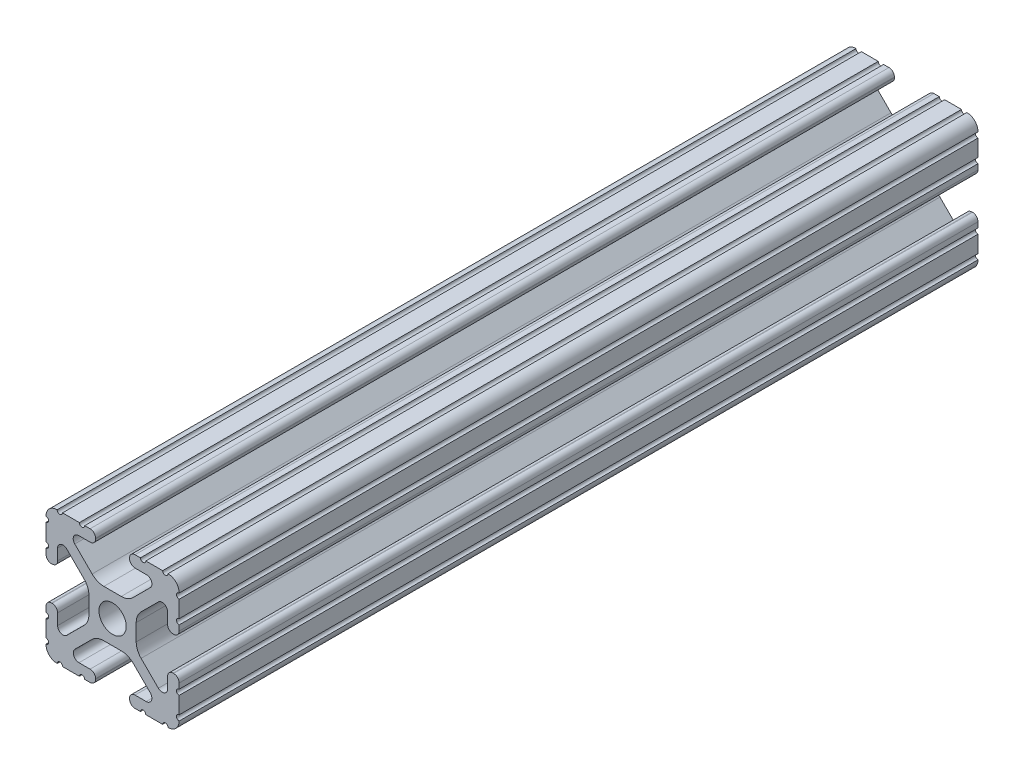
SolidWorks part; units mm, degrees
material "6061 Alloy"
ref_plane "Front Plane" through (0, 0, 0) normal (0, 0, 1) x (1, 0, 0)
ref_plane "Top Plane" through (0, 0, 0) normal (0, 1, 0) x (1, 0, 0)
ref_plane "Right Plane" through (0, 0, 0) normal (1, 0, 0) x (0, 0, -1)
sketch "Sketch1" plane through (0, 0, 0) normal (0, 0, 1) x (1, 0, 0)
  line L88 (-7.1797, -8.6452) -> (-3.9523, -5.4237)
  line L89 (-1.7093, -4.4958) -> (1.7093, -4.4958)
  line L90 (3.9523, -5.4237) -> (7.1797, -8.6452)
  line L91 (6.4164, -10.4902) -> (4.2875, -10.4902)
  line L92 (3.2385, -11.5392) -> (3.2385, -11.651)
  line L93 (4.2875, -12.7) -> (5.3171, -12.7)
  line L94 (6.3331, -12.7) -> (9.5504, -12.7)
  line L95 (12.7, -9.5504) -> (12.7, -6.3331)
  line L96 (12.7, -5.3171) -> (12.7, -4.2875)
  line L97 (11.651, -3.2385) -> (11.5392, -3.2385)
  line L98 (10.4902, -4.2875) -> (10.4902, -6.4021)
  line L99 (8.7371, -7.1294) -> (5.441, -3.8408)
  line L100 (4.5085, -1.5932) -> (4.5085, 1.5932)
  line L101 (5.441, 3.8408) -> (8.7371, 7.1294)
  line L102 (10.4902, 6.4021) -> (10.4902, 4.2875)
  line L103 (11.5392, 3.2385) -> (11.651, 3.2385)
  line L104 (12.7, 4.2875) -> (12.7, 5.3171)
  line L105 (12.7, 6.3331) -> (12.7, 9.5504)
  line L106 (9.5504, 12.7) -> (6.3331, 12.7)
  line L107 (5.3171, 12.7) -> (4.2875, 12.7)
  line L108 (3.2385, 11.651) -> (3.2385, 11.5392)
  line L109 (4.2875, 10.4902) -> (6.4768, 10.4902)
  line L110 (7.207, 8.7244) -> (3.8983, 5.4232)
  line L111 (1.6558, 4.4958) -> (-1.6558, 4.4958)
  line L112 (-3.8983, 5.4232) -> (-7.207, 8.7244)
  line L113 (-6.4768, 10.4902) -> (-4.2875, 10.4902)
  line L114 (-3.2385, 11.5392) -> (-3.2385, 11.651)
  line L115 (-4.2875, 12.7) -> (-5.3171, 12.7)
  line L116 (-6.3331, 12.7) -> (-9.5504, 12.7)
  line L117 (-12.7, 9.5504) -> (-12.7, 6.3331)
  line L118 (-12.7, 5.3171) -> (-12.7, 4.2875)
  line L119 (-11.651, 3.2385) -> (-11.5392, 3.2385)
  line L120 (-10.4902, 4.2875) -> (-10.4902, 6.4021)
  line L121 (-8.7371, 7.1294) -> (-5.441, 3.8408)
  line L122 (-4.5085, 1.5932) -> (-4.5085, -1.5932)
  line L123 (-5.441, -3.8408) -> (-8.7371, -7.1294)
  line L124 (-10.4902, -6.4021) -> (-10.4902, -4.2875)
  line L125 (-11.5392, -3.2385) -> (-11.651, -3.2385)
  line L126 (-12.7, -4.2875) -> (-12.7, -5.3171)
  line L127 (-12.7, -6.3331) -> (-12.7, -9.5504)
  line L128 (-9.5504, -12.7) -> (-6.3331, -12.7)
  line L129 (-5.3171, -12.7) -> (-4.2875, -12.7)
  line L130 (-3.2385, -11.651) -> (-3.2385, -11.5392)
  line L131 (-4.2875, -10.4902) -> (-6.4164, -10.4902)
  circle A1 centre (0, 0) radius 2.6035
  arc A104 (-7.1797, -8.6452) -> (-6.4164, -10.4902) centre (-6.4164, -9.4098) ccw
  arc A105 (-1.7093, -4.4958) -> (-3.9523, -5.4237) centre (-1.7093, -7.6708) ccw
  arc A106 (3.9523, -5.4237) -> (1.7093, -4.4958) centre (1.7093, -7.6708) ccw
  arc A107 (6.4164, -10.4902) -> (7.1797, -8.6452) centre (6.4164, -9.4098) ccw
  arc A108 (4.2875, -10.4902) -> (3.2385, -11.5392) centre (4.2875, -11.5392) ccw
  arc A109 (3.2385, -11.651) -> (4.2875, -12.7) centre (4.2875, -11.651) ccw
  arc A110 (6.3331, -12.7) -> (5.3171, -12.7) centre (5.8251, -12.7) ccw
  arc A111 (10.5664, -12.6998) -> (9.5504, -12.7) centre (10.0584, -12.7) ccw
  arc A112 (10.5664, -12.6998) -> (12.6998, -10.5664) centre (10.5918, -10.5918) ccw
  arc A113 (12.7, -9.5504) -> (12.6998, -10.5664) centre (12.7, -10.0584) ccw
  arc A114 (12.7, -5.3171) -> (12.7, -6.3331) centre (12.7, -5.8251) ccw
  arc A115 (12.7, -4.2875) -> (11.651, -3.2385) centre (11.651, -4.2875) ccw
  arc A116 (11.5392, -3.2385) -> (10.4902, -4.2875) centre (11.5392, -4.2875) ccw
  arc A117 (8.7371, -7.1294) -> (10.4902, -6.4021) centre (9.4628, -6.4021) ccw
  arc A118 (4.5085, -1.5932) -> (5.441, -3.8408) centre (7.6835, -1.5932) ccw
  arc A119 (5.441, 3.8408) -> (4.5085, 1.5932) centre (7.6835, 1.5932) ccw
  arc A120 (10.4902, 6.4021) -> (8.7371, 7.1294) centre (9.4628, 6.4021) ccw
  arc A121 (10.4902, 4.2875) -> (11.5392, 3.2385) centre (11.5392, 4.2875) ccw
  arc A122 (11.651, 3.2385) -> (12.7, 4.2875) centre (11.651, 4.2875) ccw
  arc A123 (12.7, 6.3331) -> (12.7, 5.3171) centre (12.7, 5.8251) ccw
  arc A124 (12.6998, 10.5664) -> (12.7, 9.5504) centre (12.7, 10.0584) ccw
  arc A125 (12.6998, 10.5664) -> (10.5664, 12.6998) centre (10.5918, 10.5918) ccw
  arc A126 (9.5504, 12.7) -> (10.5664, 12.6998) centre (10.0584, 12.7) ccw
  arc A127 (5.3171, 12.7) -> (6.3331, 12.7) centre (5.8251, 12.7) ccw
  arc A128 (4.2875, 12.7) -> (3.2385, 11.651) centre (4.2875, 11.651) ccw
  arc A129 (3.2385, 11.5392) -> (4.2875, 10.4902) centre (4.2875, 11.5392) ccw
  arc A130 (7.207, 8.7244) -> (6.4768, 10.4902) centre (6.4768, 9.4563) ccw
  arc A131 (1.6558, 4.4958) -> (3.8983, 5.4232) centre (1.6558, 7.6708) ccw
  arc A132 (-3.8983, 5.4232) -> (-1.6558, 4.4958) centre (-1.6558, 7.6708) ccw
  arc A133 (-6.4768, 10.4902) -> (-7.207, 8.7244) centre (-6.4768, 9.4563) ccw
  arc A134 (-4.2875, 10.4902) -> (-3.2385, 11.5392) centre (-4.2875, 11.5392) ccw
  arc A135 (-3.2385, 11.651) -> (-4.2875, 12.7) centre (-4.2875, 11.651) ccw
  arc A136 (-6.3331, 12.7) -> (-5.3171, 12.7) centre (-5.8251, 12.7) ccw
  arc A137 (-10.5664, 12.6998) -> (-9.5504, 12.7) centre (-10.0584, 12.7) ccw
  arc A138 (-10.5664, 12.6998) -> (-12.6998, 10.5664) centre (-10.5918, 10.5918) ccw
  arc A139 (-12.7, 9.5504) -> (-12.6998, 10.5664) centre (-12.7, 10.0584) ccw
  arc A140 (-12.7, 5.3171) -> (-12.7, 6.3331) centre (-12.7, 5.8251) ccw
  arc A141 (-12.7, 4.2875) -> (-11.651, 3.2385) centre (-11.651, 4.2875) ccw
  arc A142 (-11.5392, 3.2385) -> (-10.4902, 4.2875) centre (-11.5392, 4.2875) ccw
  arc A143 (-8.7371, 7.1294) -> (-10.4902, 6.4021) centre (-9.4628, 6.4021) ccw
  arc A144 (-4.5085, 1.5932) -> (-5.441, 3.8408) centre (-7.6835, 1.5932) ccw
  arc A145 (-5.441, -3.8408) -> (-4.5085, -1.5932) centre (-7.6835, -1.5932) ccw
  arc A146 (-10.4902, -6.4021) -> (-8.7371, -7.1294) centre (-9.4628, -6.4021) ccw
  arc A147 (-10.4902, -4.2875) -> (-11.5392, -3.2385) centre (-11.5392, -4.2875) ccw
  arc A148 (-11.651, -3.2385) -> (-12.7, -4.2875) centre (-11.651, -4.2875) ccw
  arc A149 (-12.7, -6.3331) -> (-12.7, -5.3171) centre (-12.7, -5.8251) ccw
  arc A150 (-12.6998, -10.5664) -> (-12.7, -9.5504) centre (-12.7, -10.0584) ccw
  arc A151 (-12.6998, -10.5664) -> (-10.5664, -12.6998) centre (-10.5918, -10.5918) ccw
  arc A152 (-9.5504, -12.7) -> (-10.5664, -12.6998) centre (-10.0584, -12.7) ccw
  arc A153 (-5.3171, -12.7) -> (-6.3331, -12.7) centre (-5.8251, -12.7) ccw
  arc A154 (-4.2875, -12.7) -> (-3.2385, -11.651) centre (-4.2875, -11.651) ccw
  arc A155 (-3.2385, -11.5392) -> (-4.2875, -10.4902) centre (-4.2875, -11.5392) ccw
extrude "Boss-Extrude1" add sketch "Sketch1" along normal mid plane 152.4
sketch "Sketch2" plane through (0, 0, 0) normal (0, 1, 0) x (1, 0, 0)
  line L0 (0, 63.5) -> (0, -63.5) construction
  circle A0 centre (0, 63.5) radius 3.175
  circle A1 centre (0, -63.5) radius 3.175
  point P4 (0, 0)
extrude "Cut-Extrude1" cut sketch "Sketch2" against normal through all both and the other way through all
sketch "Sketch4" plane through (0, 0, 0) normal (1, 0, 0) x (0, 0, -1)
  line L0 (0, 0) -> (25.4, 0) construction
  circle A0 centre (25.4, 0) radius 3.175
  circle A1 centre (0, 0) radius 3.175
extrude "Cut-Extrude2" cut sketch "Sketch4" against normal through all both and the other way through all
